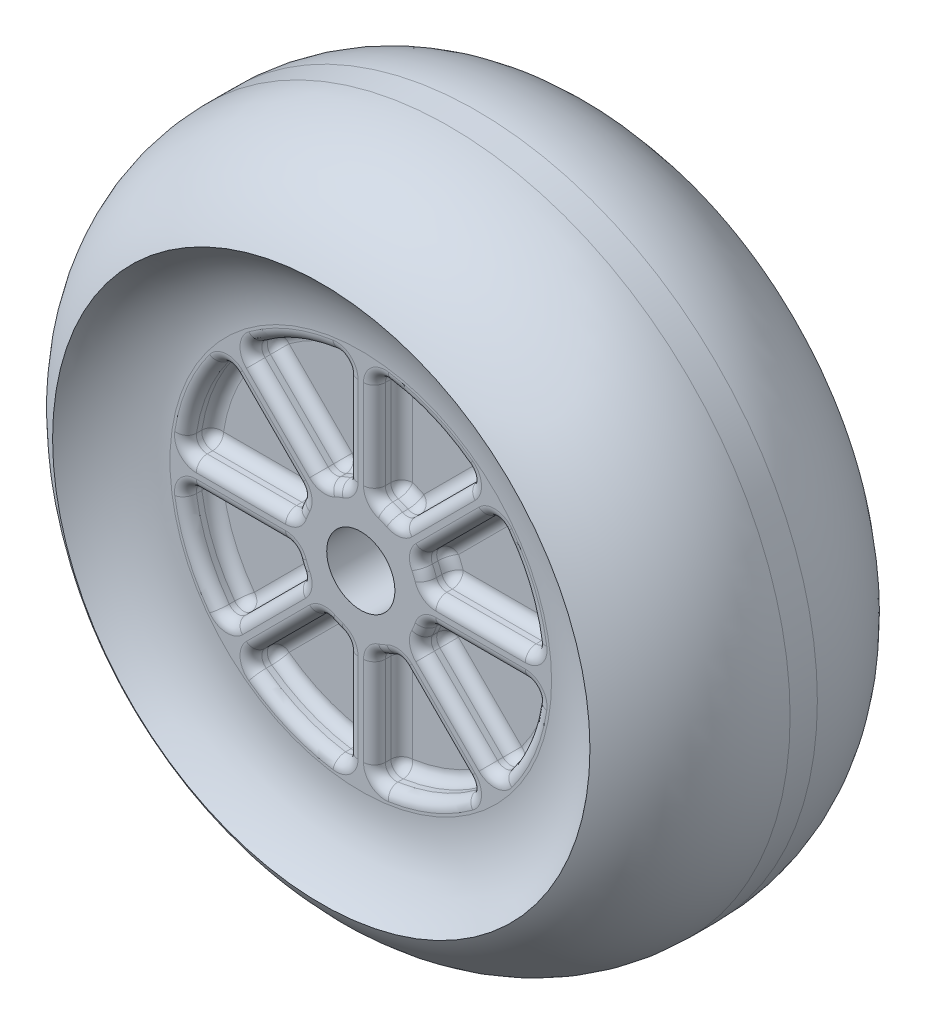
SolidWorks part; units mm, degrees
ref_plane "Front Plane" through (0, 0, 0) normal (0, 0, 1) x (1, 0, 0)
ref_plane "Top Plane" through (0, 0, 0) normal (0, 1, 0) x (1, 0, 0)
ref_plane "Right Plane" through (0, 0, 0) normal (1, 0, 0) x (0, 0, -1)
sketch "Sketch1" plane through (0, 0, 0) normal (0, 0, 1) x (1, 0, 0)
  circle A0 centre (0, 0) radius 1.5875
  circle A1 centre (0, 0) radius 3.175
  circle A2 centre (0, 0) radius 8.89
  circle A3 centre (0, 0) radius 15.875
  dimension "D1" = 31.75
  dimension "D2" = 17.78
  dimension "D3" = 6.35
  dimension "D4" = 3.175
extrude "Boss-Extrude2" add sketch "Sketch1" along normal mid plane 9.525 contours A2 A1 | A2 | A1 region at (-8.6386, 0, 0)
extrude "Boss-Extrude3" add sketch "Sketch1<4>" along normal mid plane 1.27 contours A3 A2 region at (-15.426, 0, 0)
sketch "Sketch1<4>" plane through (0, 0, 0) normal (0, 0, 1) x (1, 0, 0) same geometry as "Sketch1"
extrude "Boss-Extrude4" add sketch "Sketch1<5>" along normal mid plane 9.525 contours A1 A0 region at (-3.0852, 0, 0)
sketch "Sketch1<5>" plane through (0, 0, 0) normal (0, 0, 1) x (1, 0, 0) same geometry as "Sketch1"
sketch "Sketch2" plane through (0, 0, 0) normal (0, 0, 1) x (1, 0, 0)
  line L0 (-0.635, 3.1109) -> (-0.635, 8.2305)
  line L1 (0.635, 8.2305) -> (0.635, 3.1109)
  line L2 (1.7507, 2.6487) -> (5.3709, 6.2689)
  line L3 (6.2689, 5.3709) -> (2.6487, 1.7507)
  line L4 (3.1109, 0.635) -> (8.2305, 0.635)
  line L5 (8.2305, -0.635) -> (3.1109, -0.635)
  line L6 (2.6487, -1.7507) -> (6.2689, -5.3709)
  line L7 (5.3709, -6.2689) -> (1.7507, -2.6487)
  line L8 (0.635, -3.1109) -> (0.635, -8.2305)
  line L9 (-0.635, -8.2305) -> (-0.635, -3.1109)
  line L10 (-1.7507, -2.6487) -> (-5.3709, -6.2689)
  line L11 (-6.2689, -5.3709) -> (-2.6487, -1.7507)
  line L12 (-3.1109, -0.635) -> (-8.2305, -0.635)
  line L13 (-8.2305, 0.635) -> (-3.1109, 0.635)
  line L14 (-2.6487, 1.7507) -> (-6.2689, 5.3709)
  line L15 (-5.3709, 6.2689) -> (-1.7507, 2.6487)
  arc A0 (-6.2689, 5.3709) -> (-8.2305, 0.635) centre (0, 0) ccw
  arc A1 (-2.6487, 1.7507) -> (-3.1109, 0.635) centre (0, 0) ccw
  arc A2 (-0.635, 8.2305) -> (-5.3709, 6.2689) centre (0, 0) ccw
  arc A3 (-0.635, 3.1109) -> (-1.7507, 2.6487) centre (0, 0) ccw
  arc A4 (1.7507, 2.6487) -> (0.635, 3.1109) centre (0, 0) ccw
  arc A5 (5.3709, 6.2689) -> (0.635, 8.2305) centre (0, 0) ccw
  arc A6 (8.2305, 0.635) -> (6.2689, 5.3709) centre (0, 0) ccw
  arc A7 (3.1109, 0.635) -> (2.6487, 1.7507) centre (0, 0) ccw
  arc A8 (2.6487, -1.7507) -> (3.1109, -0.635) centre (0, 0) ccw
  arc A9 (6.2689, -5.3709) -> (8.2305, -0.635) centre (0, 0) ccw
  arc A10 (0.635, -8.2305) -> (5.3709, -6.2689) centre (0, 0) ccw
  arc A11 (-5.3709, -6.2689) -> (-0.635, -8.2305) centre (0, 0) ccw
  arc A12 (-8.2305, -0.635) -> (-6.2689, -5.3709) centre (0, 0) ccw
  arc A13 (-3.1109, -0.635) -> (-2.6487, -1.7507) centre (0, 0) ccw
  arc A14 (-1.7507, -2.6487) -> (-0.635, -3.1109) centre (0, 0) ccw
  arc A15 (0.635, -3.1109) -> (1.7507, -2.6487) centre (0, 0) ccw
  point P38 (0, 0)
  dimension "D1" = 6.35
  dimension "D2" = 16.51
  dimension "D3" = 1.27
  dimension "D4" = 8
extrude "Cut-Extrude2" cut sketch "Sketch2" against normal blind 1.27 from surface starting at face at (8.89, 0, 4.7625)
extrude "Cut-Extrude3" cut sketch "Sketch2<2>" along normal blind 1.27 from surface starting at face at (8.89, 0, -4.7625)
sketch "Sketch2<2>" plane through (0, 0, 0) normal (0, 0, 1) x (1, 0, 0) same geometry as "Sketch2"
sketch "Sketch3" plane through (0, 0, 0) normal (1, 0, 0) x (0, 0, -1)
  line L0 (0.635, 15.875) -> (0.635, 8.89)
  line L1 (0.635, -15.875) -> (0.635, 15.875) construction
  line L2 (0.635, 8.89) -> (4.7625, 8.89)
  line L3 (0, 15.875) -> (0, -15.875) construction
  line L4 (0.635, 15.875) -> (-0.635, 15.875) construction
  line L5 (-0.635, -15.875) -> (0.635, -15.875) construction
  line L6 (-0.635, 8.89) -> (-4.7625, 8.89)
  line L7 (-0.635, 15.875) -> (-0.635, 8.89)
  arc A0 (4.7625, 8.89) -> (6.6037, 12.5184) centre (9.2583, 8.89) cw
  arc A1 (0.635, 15.875) -> (6.6037, 12.5184) centre (0.635, 8.89) cw
  arc A2 (-0.635, 15.875) -> (-6.6037, 12.5184) centre (-0.635, 8.89) ccw
  arc A3 (-4.7625, 8.89) -> (-6.6037, 12.5184) centre (-9.2583, 8.89) ccw
  point P15 (0, 0)
  point P16 (0, 0)
  dimension "D2" = 4.4958
  dimension "D1" = 6.985
revolve "Revolve1" add sketch "Sketch3" angle 360 about axis through (0, 0, 4.7625) along (0, 0, -1)
fillet "Fillet2" radius 0.508 177 edges at (-0.635, 5.6707, 4.7625) (-3.1591, 7.6266, 4.7625) (-3.5608, 4.4588, 3.4925) (-3.1591, 7.6266, 3.4925) (-0.635, 5.6707, 3.4925) (-1.215, 2.9333, 3.4925) (-1.215, 2.9333, 4.7625) (-0.635, 8.2305, 4.1275) (-1.7507, 2.6487, 4.1275) (-5.3709, 6.2689, 4.1275) (-0.635, 3.1109, 4.1275) (3.1591, -7.6266, 4.7625) (5.6707, -0.635, 4.7625) (5.6707, 0.635, 4.7625) (7.6266, 3.1591, 4.7625) (1.215, -2.9333, 4.7625) (0.635, -5.6707, 4.7625) (1.215, -2.9333, 3.4925) (0.635, -5.6707, 3.4925) (3.1591, -7.6266, 3.4925) (3.5608, -4.4588, 3.4925) (7.6266, -3.1591, 3.4925) (2.9333, -1.215, 4.7625) (2.9333, -1.215, 3.4925) (4.4588, -3.5608, 3.4925) (7.6266, -3.1591, 4.7625) (2.9333, 1.215, 4.7625) (2.9333, 1.215, 3.4925) (4.4588, -3.5608, 4.7625) (5.6707, -0.635, 3.4925) (5.6707, 0.635, 3.4925) (7.6266, 3.1591, 3.4925) (4.4588, 3.5608, 3.4925) (-6.2689, 5.3709, 4.1275) (-8.2305, -0.635, 4.1275) (-8.2305, 0.635, 4.1275) (-6.2689, -5.3709, 4.1275) (-5.3709, -6.2689, 4.1275) (8.2305, 0.635, 4.1275) (-1.7507, -2.6487, 4.1275) (0.635, -3.1109, 4.1275) (1.7507, -2.6487, 4.1275) (5.3709, -6.2689, 4.1275) (-0.635, -8.2305, 4.1275) (-3.1109, 0.635, 4.1275) (-2.6487, 1.7507, 4.1275) (-2.6487, -1.7507, 4.1275) (-3.1109, -0.635, 4.1275) (-0.635, -3.1109, 4.1275) (8.2305, -0.635, 4.1275) (5.3709, 6.2689, 4.1275) (6.2689, 5.3709, 4.1275) (3.1109, -0.635, 4.1275) (2.6487, 1.7507, 4.1275) (6.2689, -5.3709, 4.1275) (0.635, -8.2305, 4.1275) (3.1109, 0.635, 4.1275) (2.6487, -1.7507, 4.1275) (0.635, 3.1109, 4.1275) (1.7507, 2.6487, 4.1275) (0.635, 8.2305, 4.1275) (-1.215, -2.9333, 4.7625) (1.215, 2.9333, 4.7625) (-2.9333, -1.215, 4.7625) (-2.9333, 1.215, 4.7625) (-3.5608, -4.4588, 4.7625) (-5.6707, -0.635, 4.7625) (-5.6707, 0.635, 4.7625) (-3.1591, -7.6266, 4.7625) (3.1591, 7.6266, 4.7625) (-7.6266, -3.1591, 4.7625) (-7.6266, 3.1591, 4.7625) (0.635, 5.6707, 3.4925) (3.1591, 7.6266, 3.4925) (3.5608, 4.4588, 3.4925) (1.215, 2.9333, 3.4925) (-5.6707, 0.635, 3.4925) (-7.6266, 3.1591, 3.4925) (-4.4588, 3.5608, 3.4925) (-2.9333, 1.215, 3.4925) (-4.4588, -3.5608, 3.4925) (-7.6266, -3.1591, 3.4925) (-5.6707, -0.635, 3.4925) (-2.9333, -1.215, 3.4925) (-0.635, -5.6707, 3.4925) (-3.1591, -7.6266, 3.4925) (-3.5608, -4.4588, 3.4925) (-1.215, -2.9333, 3.4925) (3.5608, 4.4588, -4.7625) (4.4588, -3.5608, -4.7625) (3.5608, -4.4588, -4.7625) (0.635, -5.6707, -4.7625) (-0.635, -5.6707, -4.7625) (-3.5608, -4.4588, -4.7625) (-5.6707, 0.635, -4.7625) (-4.4588, 3.5608, -4.7625) (-4.4588, -3.5608, -4.7625) (-3.1109, -0.635, -4.1275) (-2.6487, -1.7507, -4.1275) (-2.9333, -1.215, -4.7625) (-2.6487, 1.7507, -4.1275) (-3.1109, 0.635, -4.1275) (-2.9333, 1.215, -4.7625) (-0.635, 3.1109, -4.1275) (-1.7507, 2.6487, -4.1275) (-1.215, 2.9333, -4.7625) (2.6487, -1.7507, -4.1275) (3.1109, -0.635, -4.1275) (2.9333, -1.215, -4.7625) (3.1109, 0.635, -4.1275) (2.6487, 1.7507, -4.1275) (2.9333, 1.215, -4.7625) (1.7507, 2.6487, -4.1275) (0.635, 3.1109, -4.1275) (1.215, 2.9333, -4.7625) (-1.7507, -2.6487, -4.1275) (-0.635, -3.1109, -4.1275) (-1.215, -2.9333, -4.7625) (0.635, -3.1109, -4.1275) (1.7507, -2.6487, -4.1275) (1.215, -2.9333, -4.7625) (0.635, 8.2305, -4.1275) (5.3709, 6.2689, -4.1275) (3.1591, 7.6266, -4.7625) (6.2689, 5.3709, -4.1275) (8.2305, 0.635, -4.1275) (7.6266, 3.1591, -4.7625) (8.2305, -0.635, -4.1275) (6.2689, -5.3709, -4.1275) (7.6266, -3.1591, -4.7625) (5.3709, -6.2689, -4.1275) (0.635, -8.2305, -4.1275) (3.1591, -7.6266, -4.7625) (-0.635, -8.2305, -4.1275) (-5.3709, -6.2689, -4.1275) (-3.1591, -7.6266, -4.7625) (-5.3709, 6.2689, -4.1275) (-0.635, 8.2305, -4.1275) (-3.1591, 7.6266, -4.7625) (-8.2305, 0.635, -4.1275) (-6.2689, 5.3709, -4.1275) (-7.6266, 3.1591, -4.7625) (-6.2689, -5.3709, -4.1275) (-8.2305, -0.635, -4.1275) (-7.6266, -3.1591, -4.7625) (-3.5608, -4.4588, -3.4925) (-3.1591, -7.6266, -3.4925) (-0.635, -5.6707, -3.4925) (-1.215, -2.9333, -3.4925) (0.635, -5.6707, -3.4925) (3.1591, -7.6266, -3.4925) (3.5608, -4.4588, -3.4925) (1.215, -2.9333, -3.4925) (-5.6707, -0.635, -3.4925) (-7.6266, -3.1591, -3.4925) (-4.4588, -3.5608, -3.4925) (-2.9333, -1.215, -3.4925) (4.4588, -3.5608, -3.4925) (7.6266, -3.1591, -3.4925) (5.6707, -0.635, -3.4925) (2.9333, -1.215, -3.4925) (5.6707, 0.635, -3.4925) (7.6266, 3.1591, -3.4925) (4.4588, 3.5608, -3.4925) (2.9333, 1.215, -3.4925) (3.5608, 4.4588, -3.4925) (3.1591, 7.6266, -3.4925) (0.635, 5.6707, -3.4925) (1.215, 2.9333, -3.4925) (-0.635, 5.6707, -3.4925) (-3.1591, 7.6266, -3.4925) (-3.5608, 4.4588, -3.4925) (-1.215, 2.9333, -3.4925) (-4.4588, 3.5608, -3.4925) (-7.6266, 3.1591, -3.4925) (-5.6707, 0.635, -3.4925) (-2.9333, 1.215, -3.4925)
